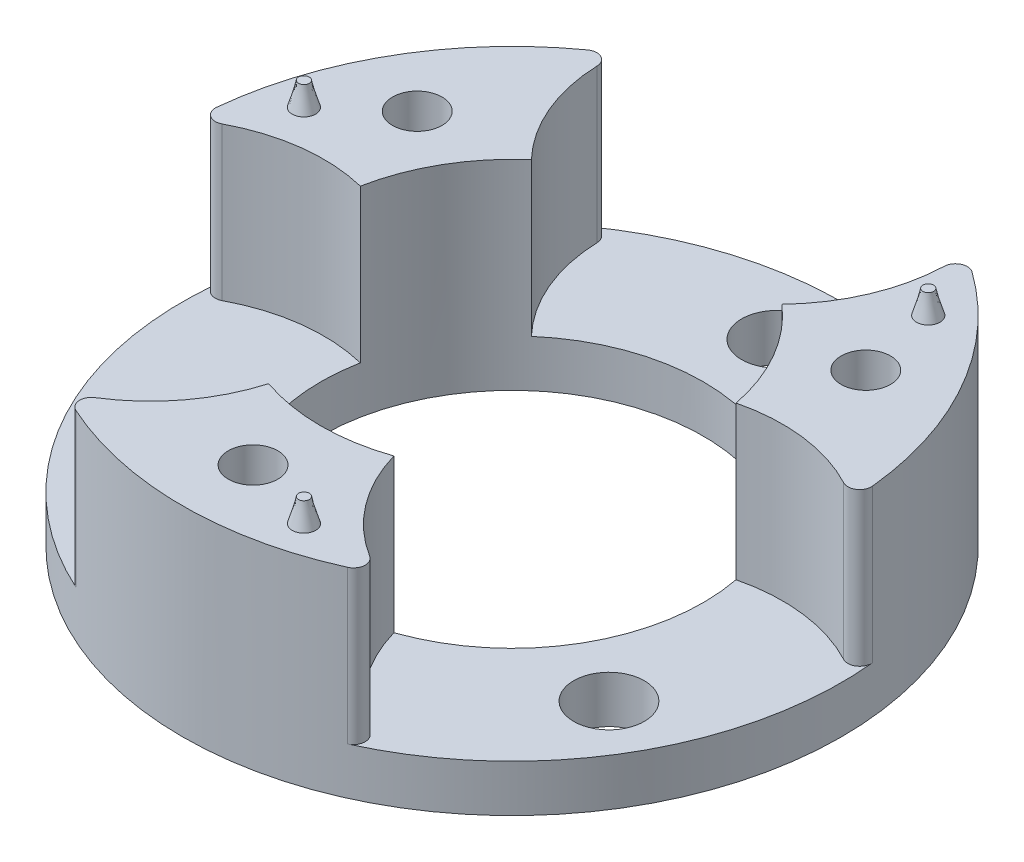
SolidWorks part; units mm, degrees
ref_plane "Plano frontal" through (0, 0, 0) normal (0, 0, 1) x (1, 0, 0)
ref_plane "Plano superior" through (0, 0, 0) normal (0, 1, 0) x (1, 0, 0)
ref_plane "Plano direito" through (0, 0, 0) normal (1, 0, 0) x (0, 0, -1)
sketch "Esboço1" plane through (0, 0, 0) normal (0, 1, 0) x (1, 0, 0)
  circle A0 centre (0, 0) radius 28
  dimension "D1" = 56
extrude "Ressalto-extrusão1" add sketch "Esboço1" along normal blind 4
sketch "Esboço2" plane through (0, 4, 0) normal (0, 1, 0) x (1, 0, 0)
  line L0 (0, 0) -> (0, 28) construction
  circle A0 centre (0, 0) radius 28 construction
  circle A1 centre (0, 22.5) radius 3
  dimension "D1" = 6
  dimension "D2" = 22.5
extrude "Corte-extrusão1" cut sketch "Esboço2" against normal through all
pattern_circular "PadrãoCircular1" count 3 over 360 about axis through (0, 4, 0) along (0, 1, 0) of "Corte-extrusão1"
sketch "Esboço3" plane through (0, 4, 0) normal (0, 1, 0) x (1, 0, 0)
  circle A0 centre (0, 0) radius 16.25
  dimension "D1" = 32.5
extrude "Corte-extrusão2" cut sketch "Esboço3" against normal through all
sketch "Esboço4" plane through (0, 4, 0) normal (0, 1, 0) x (1, 0, 0)
  arc A0 (10.6387, 12.2833) -> (14.7406, 21.9732) centre (0, 22.5) ccw
  circle A2 centre (0, 0) radius 28 construction
  arc A3 (27.8635, 2.7611) -> (16.3229, 22.75) centre (0, 0) ccw
  circle A4 centre (0, 0) radius 16.25 construction
  arc A5 (15.957, 3.0717) -> (10.6387, 12.2833) centre (0, 0) ccw
  arc A6 (26.3997, 1.7791) -> (15.957, 3.0717) centre (19.4856, -11.25) ccw
  arc A7 (14.7406, 21.9732) -> (16.3229, 22.75) centre (15.74, 21.9375) cw
  arc A8 (26.3997, 1.7791) -> (27.8635, 2.7611) centre (26.8684, 2.6624) ccw
  dimension "D1" = 29.5
  dimension "D2" = 14.75
  dimension "D3" = 1
extrude "Ressalto-extrusão2" add sketch "Esboço4" along normal blind 13
pattern_circular "PadrãoCircular2" count 3 over 360 about axis through (0, 4, 0) along (0, 1, 0) of "Ressalto-extrusão2"
sketch "Esboço5" plane through (0, 17, 0) normal (0, 1, 0) x (1, 0, 0)
  line L0 (0, 0) -> (0, -28) construction
  arc A0 (-11.5406, -25.5111) -> (11.5406, -25.5111) centre (0, 0) ccw construction
  circle A1 centre (0, -22) radius 2.1
  dimension "D1" = 4.2
  dimension "D2" = 22
extrude "Corte-extrusão3" cut sketch "Esboço5" against normal blind 8
pattern_circular "PadrãoCircular3" count 3 over 360 about axis through (0, 4, 0) along (0, 1, 0) of "Corte-extrusão3"
sketch "Esboço7" plane through (0, 17, 0) normal (0, 1, 0) x (1, 0, 0)
  line L0 (0, 0) -> (0, -28) construction
  line L1 (0, -22) -> (6.4725, -24.1493) construction
  circle A1 centre (0, -22) radius 2.1 construction
  arc A2 (-11.5406, -25.5111) -> (11.5406, -25.5111) centre (0, 0) ccw construction
  circle A3 centre (6.4725, -24.1493) radius 1
  dimension "D2" = 6.82
  dimension "D3" = 2
  dimension "D1" = 108.37
ref_plane "Plano1" through (0, 19, 0) normal (0, 1, 0) x (1, 0, 0)
sketch "Esboço8" plane through (0, 19, 0) normal (0, 1, 0) x (1, 0, 0)
  circle A0 centre (6.4725, -24.1493) radius 0.46
  dimension "D1" = 0.92
loft "Loft1" add profiles "Esboço7", "Esboço8" connector at (7.4716, 17, 24.1085) connector at (6.8588, 19, 24.399)
pattern_circular "PadrãoCircular4" count 3 over 360 about axis through (0, 4, 0) along (0, 1, 0) of "Loft1"
